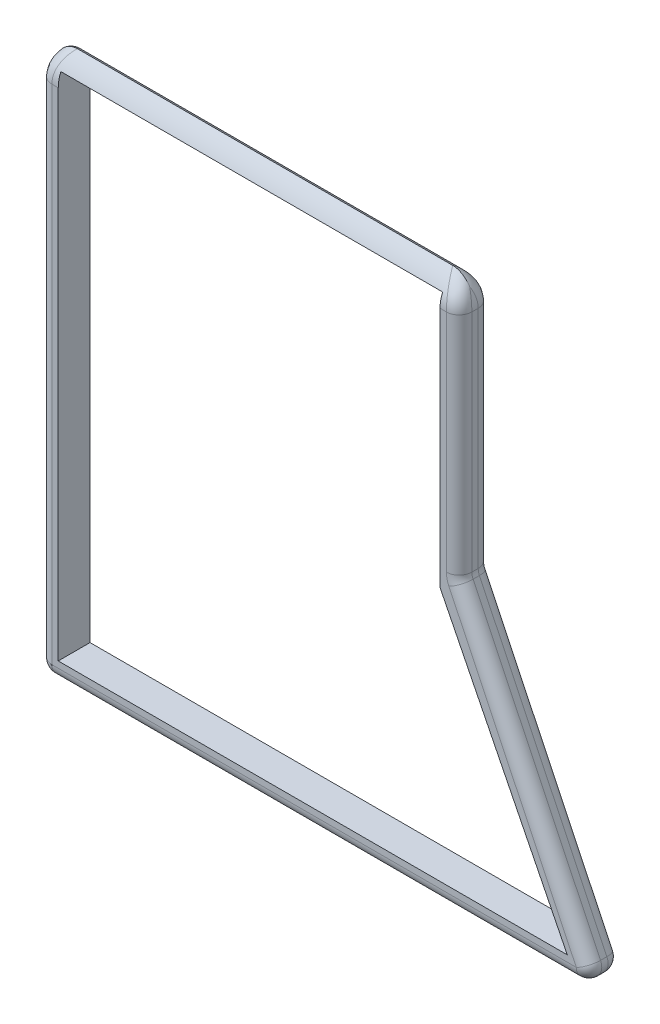
SolidWorks part; units mm, degrees
ref_plane "Front Plane" through (0, 0, 0) normal (0, 0, 1) x (1, 0, 0)
ref_plane "Top Plane" through (0, 0, 0) normal (0, 1, 0) x (1, 0, 0)
ref_plane "Right Plane" through (0, 0, 0) normal (1, 0, 0) x (0, 0, -1)
sketch "Sketch1" plane through (0, 0, 0) normal (0, 0, 1) x (1, 0, 0)
  line L0 (0.3, 0) -> (0.5, -0.4)
  line L1 (-0.3, 0.4) -> (0.3, 0.4)
  line L2 (-0.3, 0.4) -> (-0.3, -0.4)
  line L3 (-0.3, -0.4) -> (0.3, -0.4)
  line L4 (0.3, 0.4) -> (0.3, 0)
  line L5 (-0.3, 0.4) -> (0.3, -0.4) construction
  line L6 (-0.3, -0.4) -> (0.3, 0.4) construction
  line L7 (0.5, -0.4) -> (0.3, -0.4)
  line L8 (-0.33, 0.4213) -> (-0.33, -0.43)
  line L9 (-0.33, -0.43) -> (0.5459, -0.43)
  line L10 (0.5459, -0.43) -> (0.33, 0.0213)
  line L11 (0.33, 0.0213) -> (0.33, 0.43)
  line L12 (0.33, 0.43) -> (-0.33, 0.43)
  line L13 (-0.33, 0.43) -> (-0.33, 0.4213)
  point P0 (0, 0)
  point P10 (0.33, 0.2257)
  dimension "D1" = 0.8
  dimension "D2" = 0.6
  dimension "D3" = 0.2
  dimension "D4" = 0.03
  dimension "D5" = 0.03
  dimension "D6" = 0.03
  dimension "D7" = 0.03
  dimension "D8" = 181
extrude "Boss-Extrude1" add sketch "Sketch1" along normal mid plane 0.05
fillet "Fillet4" radius 0.05 4 edges at (0.33, 0.43, 0) (0, 0.43, 0.025) (-0.33, 0.43, 0) (0, 0.43, -0.025)
fillet "Fillet5" radius 0.02 7 edges at (0.438, -0.2043, 0.025) (0.438, -0.2043, -0.025) (0.3233, 0.405, 0.0183) (0.3233, 0.405, -0.0183) (0.33, 0.0213, 0) (0.33, 0.2007, 0.025) (0.33, 0.2007, -0.025)
fillet "Fillet6" radius 0.02 5 edges at (-0.3233, 0.405, -0.0183) (-0.3233, 0.405, 0.0183) (-0.33, -0.43, 0) (-0.33, -0.025, -0.025) (-0.33, -0.025, 0.025)
fillet "Fillet7" radius 0.02 7 edges at (-0.3241, -0.4241, 0.0191) (-0.3241, -0.4241, -0.0191) (0.5394, -0.43, 0.0191) (0.5459, -0.43, 0) (0.5394, -0.43, -0.0191) (0.1069, -0.43, -0.025) (0.1069, -0.43, 0.025)
